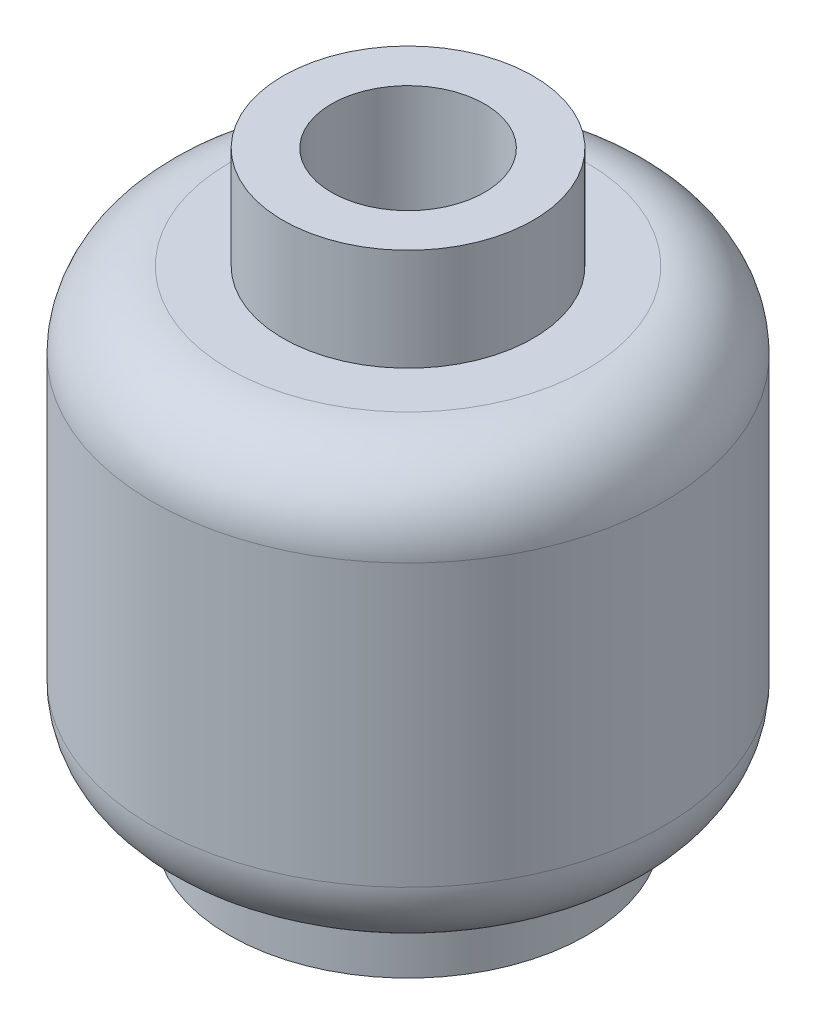
SolidWorks part; units mm, degrees
ref_plane "Front Plane" through (0, 0, 0) normal (0, 0, 1) x (1, 0, 0)
ref_plane "Top Plane" through (0, 0, 0) normal (0, 1, 0) x (1, 0, 0)
ref_plane "Right Plane" through (0, 0, 0) normal (1, 0, 0) x (0, 0, -1)
sketch "Sketch1" plane through (0, 0, 0) normal (0, 0, 1) x (1, 0, 0)
  line L0 (0, 45.7875) -> (2.45, 45.7875)
  line L1 (0, -55) -> (0, 55) construction
  line L2 (2.45, 45.7875) -> (2.45, 43.7875)
  line L3 (2.45, 43.7875) -> (3.5, 43.7875)
  line L4 (5, 42.2875) -> (5, 36.7875)
  line L5 (3.5, 35.2875) -> (3.5, 34.1875)
  line L6 (3.5, 34.1875) -> (0, 34.1875)
  line L7 (0, 45.7875) -> (0, 34.1875)
  arc A0 (5, 42.2875) -> (3.5, 43.7875) centre (3.5, 42.2875) ccw
  arc A1 (3.5, 35.2875) -> (5, 36.7875) centre (3.5, 36.7875) ccw
  dimension "D3" = 3
  dimension "D8" = 3.5
  dimension "D7" = 3
  dimension "D1" = 2.45
  dimension "D2" = 2
  dimension "D4" = 5
  dimension "D5" = 8.5
  dimension "D6" = 1.1
ref_axis "Axis2" through (0, -16.6512, 0) along (0, 1, 0)
revolve "Revolve1" add sketch "Sketch1" angle 360 about L7
sketch "Sketch8" plane through (0, 34.1875, 0) normal (0, -1, 0) x (1, 0, 0)
  circle A0 centre (0, 0) radius 2.55
  circle A1 centre (0, 0) radius 5 construction
  dimension "D1" = 2.45
extrude "Cut-Extrude1" cut sketch "Sketch8" against normal blind 8.5 draft 1
sketch "Sketch9" plane through (0, 45.7875, 0) normal (0, 1, 0) x (1, 0, 0)
  circle A0 centre (0, 0) radius 1.5
extrude "Cut-Extrude2" cut sketch "Sketch9" against normal blind 2
sketch "Sketch10" plane through (0, 43.7875, 0) normal (0, 1, 0) x (1, 0, 0)
  line L0 (-0.4, 1.4457) -> (-0.4, 0.3499)
  line L1 (-0.4, 0.3499) -> (-1.4753, -0.271)
  line L2 (0.4, 1.4457) -> (0.4, 0.3499)
  line L3 (0.4, 0.3499) -> (1.4753, -0.271)
  line L4 (-1.1248, -0.9924) -> (0, -0.343)
  line L5 (0, -5.5) -> (0, 5.5) construction
  line L6 (0, -0.343) -> (1.1248, -0.9924)
  circle A0 centre (0, 0) radius 1.5 construction
  circle A1 centre (0, 0) radius 1.5 construction
  circle M1 centre (0, 0) radius 1.5
  dimension "D1" = 0.8
  dimension "D2" = 0.8
  dimension "D3" = 0.4
  dimension "D4" = 0.8
  dimension "D5" = 120
  dimension "D6" = 120
extrude "Cut-Extrude5" cut sketch "Sketch10" against normal through all and the other way through all contours L1 L0 M1 | L2 L3 M1 | L6 L4 M1 region at (-0.9098, 43.7875, -0.587) region at (0.9098, 43.7875, -0.587) region at (0, 43.7875, 0.9958)
